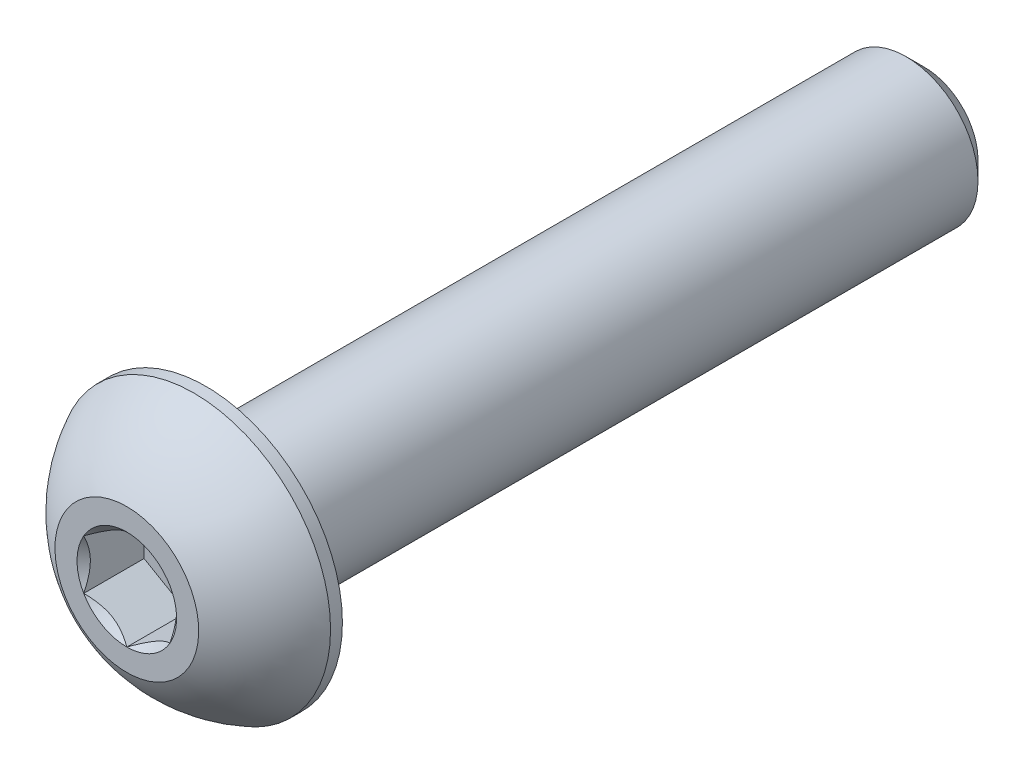
SolidWorks part; units mm, degrees
material "Alloy Steel"
ref_plane "Front Plane" through (0, 0, 0) normal (0, 0, 1) x (1, 0, 0)
ref_plane "Top Plane" through (0, 0, 0) normal (0, 1, 0) x (1, 0, 0)
ref_plane "Right Plane" through (0, 0, 0) normal (1, 0, 0) x (0, 0, -1)
sketch "Sketch1" plane through (0, 0, 0) normal (1, 0, 0) x (0, 0, -1)
  line L0 (-13.875, 0) -> (13.875, 0) construction
  line L1 (-11.125, 4.75) -> (-11.125, -4.75) construction
  line L2 (13.875, 2.5) -> (13.875, -2.5) construction
  line L3 (13.825, 2.5866) -> (14.225, 1.8938) construction
  line L4 (14.225, 1.8938) -> (14.625, 2.5866) construction
  line L5 (14.625, 2.5866) -> (13.825, 2.5866) construction
  line L6 (13.875, 2.5) -> (14.575, 2.5) construction
  line L7 (14.225, 2.5866) -> (14.225, 2.5) construction
  line L8 (14.225, 2.5) -> (14.225, 1.9804) construction
  line L9 (14.225, 1.9804) -> (14.225, 1.8938) construction
  line L10 (14.175, 1.9804) -> (14.275, 1.9804)
  line L11 (13.85, 2.5433) -> (14.6, 2.5433)
  line L12 (14.275, 1.9804) -> (14.6, 2.5433)
  line L13 (14.175, 1.9804) -> (13.85, 2.5433)
  line L14 (-13.875, 1.5) -> (-13.875, -1.5) construction
  line L15 (13.875, 2.5) -> (-11.125, 2.5) construction
  point P3 (-11.125, 0)
  point P6 (-11.775, 0)
  point P21 (14.225, 2.5433)
  point P24 (-11.5375, 4.75)
  point P25 (11.875, -2.5)
  point P26 (-13.875, 2.5)
  dimension "Head Height" = 2.75
  dimension "Length" = 25
  dimension "Head Dia" = 9.5
  dimension "Thread Dia" = 5
  dimension "Pitch" = 0.8
  dimension "D2" = 0.1
  dimension "Drive Size" = 3
  dimension "D1" = 2.1
  dimension "D3" = 0.4125
  dimension "D4" = 2
sketch "Sketch2" plane through (0, 0, 0) normal (1, 0, 0) x (0, 0, -1)
  line L0 (-13.875, 0) -> (13.875, 0)
  line L1 (13.875, 0) -> (13.875, 1.86)
  line L2 (13.875, 2.5) -> (13.875, -2.5) construction
  line L3 (13.875, 1.86) -> (13.235, 2.5)
  line L4 (13.235, 2.5) -> (-11.125, 2.5)
  line L5 (-11.125, 4.75) -> (-11.125, -4.75) construction
  line L6 (-11.125, 2.5) -> (-11.125, 4.75)
  line L7 (-11.125, 4.75) -> (-11.5375, 4.75)
  line L8 (13.875, 2.5) -> (14.575, 2.5) construction
  line L9 (-13.875, 0) -> (-13.875, 2.5)
  arc A0 (-13.875, 2.5) -> (-11.5375, 4.75) centre (-9.2169, 0) cw
  dimension "D1" = 0.64
  dimension "D2" = 45
revolve "Revolve1" add sketch "Sketch2" angle 360 about L0
sketch "Sketch3" plane through (0, 0, 13.875) normal (0, 0, 1) x (1, 0, 0)
  line L1 (0, 1.7321) -> (-1.5, 0.866)
  line L2 (-1.5, 0.866) -> (-1.5, -0.866)
  line L3 (-1.5, -0.866) -> (0, -1.7321)
  line L4 (0, -1.7321) -> (1.5, -0.866)
  line L5 (1.5, -0.866) -> (1.5, 0.866)
  line L6 (1.5, 0.866) -> (0, 1.7321)
  circle A0 centre (0, 0) radius 1.5 construction
  dimension "D1" = 3
extrude "Cut-Extrude1" cut sketch "Sketch3" against normal up to vertex (2.1 mm away) up to point (0, 0, 11.775)
sketch "Sketch4" plane through (0, 0, 13.875) normal (0, 0, 1) x (1, 0, 0)
  circle A0 centre (0, 0) radius 1.7321
extrude "Cut-Extrude2" cut sketch "Sketch4" against normal blind 10 draft 45
split "Split1" [suppressed] bodies to split 106
sketch "Sketch5" [suppressed] plane through (0, 0, -13.875) normal (0, 0, -1) x (-1, 0, 0)
  circle A0 centre (0, 0) radius 2.5 construction
  circle A1 centre (0, 0) radius 2.5
curve "Helix/Spiral1" [suppressed] pitch 0.8 height 25.8 turns 32.25
sketch "Sketch6" [suppressed] plane through (0, 0, 0) normal (1, 0, 0) x (0, 0, -1)
  line L0 (14.175, 1.9804) -> (14.275, 1.9804) construction
  line L1 (14.175, 1.9804) -> (13.85, 2.5433) construction
  line L2 (13.85, 2.5433) -> (14.6, 2.5433) construction
  line L3 (14.275, 1.9804) -> (14.6, 2.5433) construction
  line L4 (14.175, 1.9804) -> (14.275, 1.9804)
  line L5 (14.175, 1.9804) -> (13.85, 2.5433)
  line L6 (13.85, 2.5433) -> (14.6, 2.5433)
  line L7 (14.275, 1.9804) -> (14.6, 2.5433)
sweep "Cut-Sweep1" [suppressed] cut profiles "Sketch6" path "Helix/Spiral1"
sketch "Sketch7" [suppressed] plane through (0, 0, 11.125) normal (0, 0, -1) x (-1, 0, 0)
  circle A1 centre (0, 0) radius 2.5
  circle A2 centre (0, 0) radius 2.5
  dimension "D1" = 0
extrude "Boss-Extrude1" [suppressed] add sketch "Sketch7" along normal blind 10 draft 30
equation "\"D2@Sketch1\" = \"Pitch@Sketch1\" / 8"
equation "\"D1@Sketch1\"=\"Drive Size@Sketch1\"*.7"
equation "\"D3@Sketch1\"=\"Head Height@Sketch1\"*.15"
equation "\"D1@Sketch2\"=\"Pitch@Sketch1\"*.8"
equation "\"D1@Sketch3\"=\"Drive Size@Sketch1\""
equation "\"D4@Helix/Spiral1\"=\"Pitch@Sketch1\""
equation "\"D3@Helix/Spiral1\"=\"Length@Sketch1\"+\"Pitch@Sketch1\""
equation "\"D4@Sketch1\"=\"Pitch@Sketch1\"*2.5"
